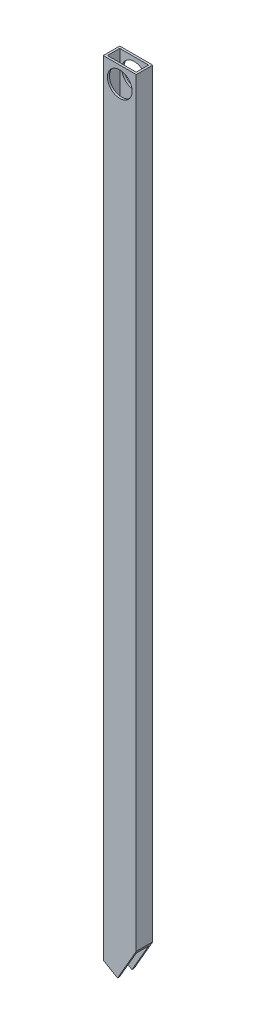
SolidWorks part; units mm, degrees
ref_plane "Front Plane" through (0, 0, 0) normal (0, 0, 1) x (1, 0, 0)
ref_plane "Top Plane" through (0, 0, 0) normal (0, 1, 0) x (1, 0, 0)
ref_plane "Right Plane" through (0, 0, 0) normal (1, 0, 0) x (0, 0, -1)
sketch "Sketch1" plane through (0, 0, 0) normal (0, 1, 0) x (1, 0, 0)
  line L0 (-22.225, 9.525) -> (-22.225, 12.7) construction
  line L1 (-25.4, -12.7) -> (25.4, -12.7)
  line L2 (-25.4, -12.7) -> (-25.4, 12.7)
  line L3 (-25.4, 12.7) -> (25.4, 12.7)
  line L4 (25.4, -12.7) -> (25.4, 12.7)
  line L5 (-25.4, -12.7) -> (25.4, 12.7) construction
  line L6 (-25.4, 12.7) -> (25.4, -12.7) construction
  line L7 (-22.225, -9.525) -> (22.225, -9.525)
  line L8 (-22.225, -9.525) -> (-22.225, 9.525)
  line L9 (-22.225, 9.525) -> (22.225, 9.525)
  line L10 (22.225, -9.525) -> (22.225, 9.525)
  line L11 (-22.225, -9.525) -> (22.225, 9.525) construction
  line L12 (-22.225, 9.525) -> (22.225, -9.525) construction
  line L13 (-22.225, 9.525) -> (-25.4, 9.525) construction
  point P0 (0, 0)
  point P6 (0, 0)
  dimension "D1" = 3.175
  dimension "D2" = 50.8
  dimension "D3" = 25.4
extrude "Boss-Extrude1" add sketch "Sketch1" along normal blind 1219.2
sketch "Sketch2" plane through (0, 0, 12.7) normal (0, 0, 1) x (1, 0, 0)
  line L9 (-25.4, 0) -> (-25.4, 12.7)
  line L10 (-25.4, 1219.2) -> (-25.4, 0) construction
  line L11 (-25.4, 12.7) -> (-3.403, 0)
  line L12 (-25.4, 0) -> (25.4, 0) construction
  line L13 (-3.403, 0) -> (-25.4, 0)
  line L14 (25.4, 0) -> (-3.403, 0)
  line L15 (25.4, 0) -> (25.4, 49.8882)
  line L16 (25.4, 1219.2) -> (25.4, 0) construction
  line L17 (25.4, 49.8882) -> (-3.403, 0)
  line L18 (-25.4, 1219.2) -> (25.4, 1219.2) construction
  circle A0 centre (0, 1193.8) radius 19.05
  line M3 (-25.4, 0) -> (25.4, 0)
  line M4 (25.4, 0) -> (25.4, 1219.2)
  line M6 (-25.4, 1219.2) -> (-25.4, 0)
  dimension "D3" = 38.1
  dimension "D1" = 30
  dimension "D2" = 25.4
  dimension "D4" = 25.4
extrude "Cut-Extrude1" cut sketch "Sketch2" against normal through all contours L11 M6 M3 | L17 M4 M3 | A0 region at (15.799, 16.6294, 12.7) region at (-18.0677, 4.2333, 12.7)
